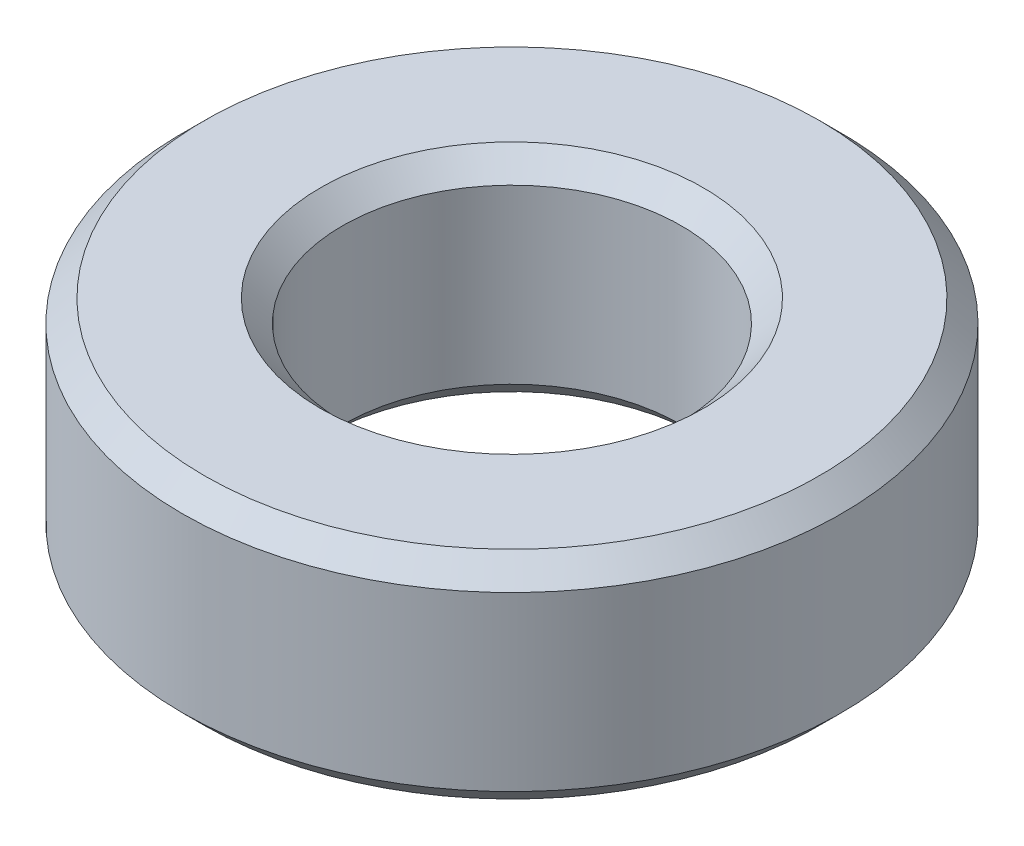
SolidWorks part; units mm, degrees
ref_plane "Front Plane" through (0, 0, 0) normal (0, 0, 1) x (1, 0, 0)
ref_plane "Top Plane" through (0, 0, 0) normal (0, 1, 0) x (1, 0, 0)
ref_plane "Right Plane" through (0, 0, 0) normal (1, 0, 0) x (0, 0, -1)
sketch "Sketch1" plane through (0, 0, 0) normal (0, 1, 0) x (1, 0, 0)
  circle A0 centre (0, 0) radius 42.5
  dimension "SLEEVE_OD" = 85
extrude "Boss-Extrude1" add sketch "Sketch1" along normal blind 27.8936
sketch "Sketch2" plane through (0, 0, 0) normal (0, 1, 0) x (1, 0, 0)
  circle A0 centre (0, 0) radius 21.8451
  dimension "BORE_D" = 43.6901
extrude "Cut-Extrude1" cut sketch "Sketch2" along normal through all
chamfer "Chamfer1" distance 2.8316 angle 45 4 edges at (0, 27.8936, 21.8451) (0, 0, 21.8451) (0, 0, 42.5) (0, 27.8936, 42.5)
